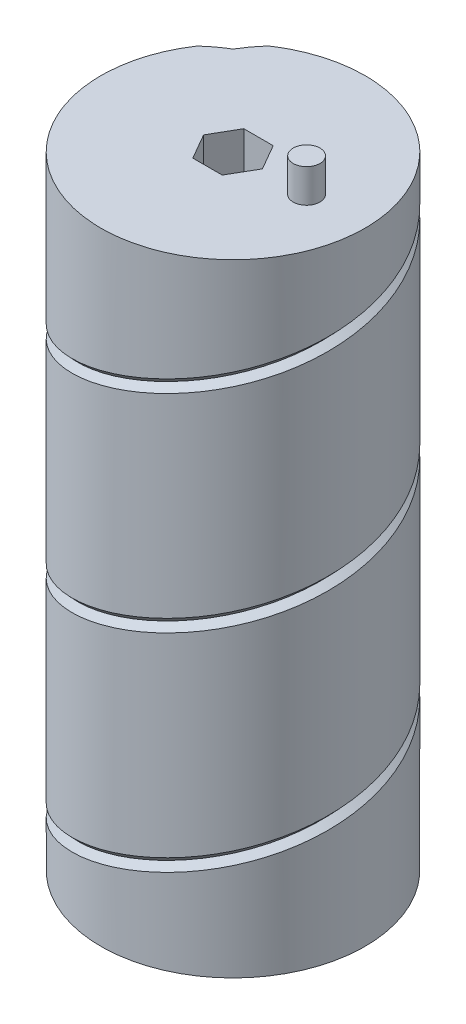
SolidWorks part; units mm, degrees
ref_plane "Front Plane" through (0, 0, 0) normal (0, 0, 1) x (1, 0, 0)
ref_plane "Top Plane" through (0, 0, 0) normal (0, 1, 0) x (1, 0, 0)
ref_plane "Right Plane" through (0, 0, 0) normal (1, 0, 0) x (0, 0, -1)
sketch "Sketch1" plane through (0, 0, 0) normal (0, 1, 0) x (1, 0, 0)
  line L0 (-19.75, 0) -> (19.75, 0) construction
  circle A0 centre (0, 0) radius 19.75
  dimension "D1" = 39.5
curve "Helix - Antenna Guide" pitch 31 height 93 radius 19.75 centre (0, 0, 0) axis (0, 1, 0) start towards (0, 0, 1)
extrude "Extrude - Main Body" add sketch "Sketch1<2>" along normal blind 93
sketch "Sketch1<2>" plane through (0, 0, 0) normal (0, 1, 0) x (1, 0, 0) same geometry as "Sketch1"
ref_point "Point2"
ref_point "Point1"
ref_plane "Plane1" through (-13.9654, 0, -13.9654) normal (-0.686, 0.2424, 0.686) x (-0.7276, -0.2285, -0.6468)
sketch "Sketch15" plane through (-13.9654, 0, -13.9654) normal (-0.686, 0.2424, 0.686) x (-0.7276, -0.2285, -0.6468)
  line L4 (0, 0) -> (0.2165, 0.8934)
  line L5 (0.2165, 0.8934) -> (-0.8934, 0.2165)
  line L8 (0, 0) -> (-0.2165, -0.8934)
  line L9 (-0.2165, -0.8934) -> (-0.8934, 0.2165)
  point P7 (-0.5549, -0.3384)
  dimension "D1" = 0.65
  dimension "D2" = 90
sweep "Cut - Antenna Wire Guide" cut profiles "Sketch15" path "Helix - Antenna Guide" align with end faces yes
sketch "Sketch23" plane through (0, 0, 0) normal (0, -1, 0) x (1, 0, 0)
  line L0 (-13.3154, -13.3154) -> (-8.3849, -14.1466)
  line L1 (-9.335, -17.4046) -> (-10.0329, -12.4535)
  arc A0 (-11.0473, -16.3713) -> (-16.3713, -11.0473) centre (0, 0) ccw construction
  arc A1 (-10.0329, -12.4535) -> (-8.3849, -14.1466) centre (-8.0525, -12.1744) cw
  arc A2 (-9.335, -17.4046) -> (-13.3154, -13.3154) centre (-14.1184, -18.0788) cw
  dimension "D2" = 2
  dimension "D1" = 2
  dimension "D3" = 5
  dimension "D4" = 5
ref_plane "Plane - Anchor Loop Exit" through (-9.335, 0, -17.4046) normal (-0.1396, 0, 0.9902) x (0.9902, 0, 0.1396)
ref_plane "Plane - Anchor Loop Peg" through (-10.0329, 0, -12.4535) normal (-0.1396, 0, 0.9902) x (0.9902, 0, 0.1396)
sketch "Sketch28" plane through (0, 93, 0) normal (0, 1, 0) x (1, 0, 0)
  circle A0 centre (11, 0) radius 2
  point P0 (0, 0)
  dimension "D1" = 4
  dimension "D2" = 11
extrude "Extruded Peg" add sketch "Sketch28" along normal blind 5
hole_wizard "Hole for Threaded Rod" positions "Sketch29" profile "Sketch30" hole size "#8" standard "ANSI Inch" end condition through all
sketch "Sketch29" plane through (0, 93, 0) normal (0, 1, 0) x (1, 0, 0)
  point P0 (0, 0)
sketch "Sketch30" plane through (0, 93, 0) normal (1, 0, 0) x (0, 0, 1)
  line L0 (0, 0) -> (0, 94.4693)
  line L1 (0, 94.4693) -> (2.2479, 94.4693)
  line L2 (2.2479, 94.4693) -> (2.2479, 0)
  line L5 (2.2479, 0) -> (0, 0)
  line L11 (0, -6.35) -> (0, 107.95) construction
  dimension "Thru Hole Dia." = 4.4958
  dimension "Thru Hole Depth" = 94.4693
sketch "Sketch31" plane through (0, 0, 0) normal (0, -1, 0) x (1, 0, 0)
  circle A0 centre (11, 0) radius 2.25
  dimension "D1" = 4.5
  dimension "D2" = 11
extrude "Cut Peg" cut sketch "Sketch31" against normal blind 5.5
sketch "Sketch32" plane through (0, 93, 0) normal (0, 1, 0) x (1, 0, 0)
  line L1 (-2.1997, -3.81) -> (2.1997, -3.81)
  line L2 (2.1997, -3.81) -> (4.3994, 0)
  line L3 (4.3994, 0) -> (2.1997, 3.81)
  line L4 (2.1997, 3.81) -> (-2.1997, 3.81)
  line L5 (-2.1997, 3.81) -> (-4.3994, 0)
  line L6 (-4.3994, 0) -> (-2.1997, -3.81)
  circle A1 centre (0, 0) radius 3.81 construction
  dimension "D1" = 7.62
extrude "Cut-Extrude1" cut sketch "Sketch32" against normal blind 26.67
equation "\"pegD\"=10"
equation "\"pegHoleD\"=0.5"
equation "\"pegHoleOffset\"=0.5"
